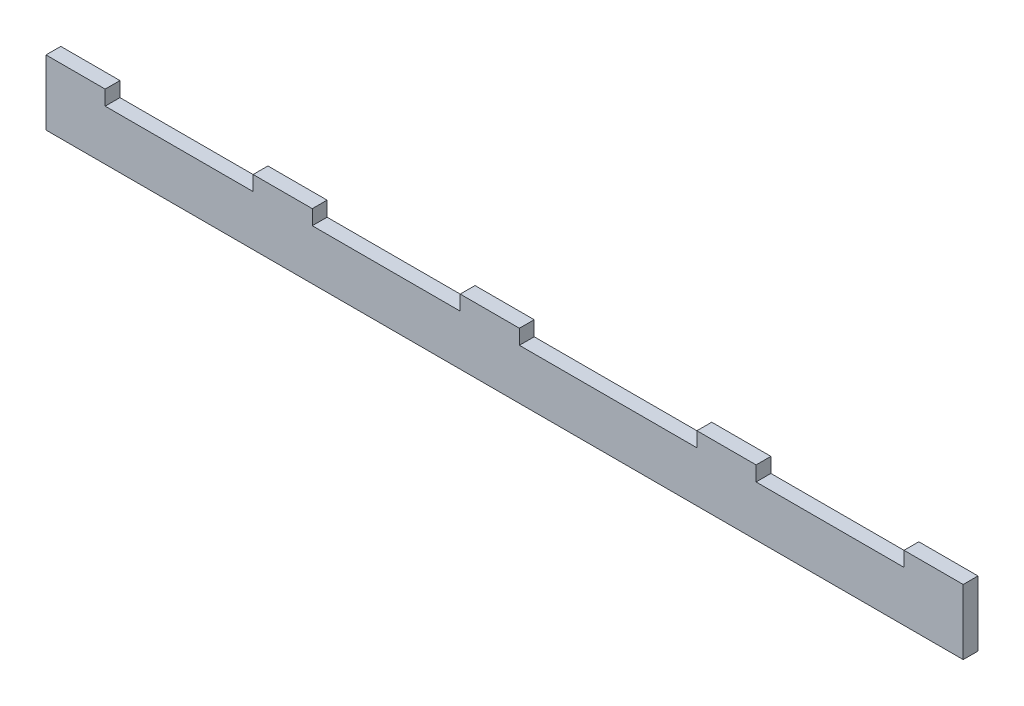
SolidWorks part; units mm, degrees
ref_plane "Plan de face" through (0, 0, 0) normal (0, 0, 1) x (1, 0, 0)
ref_plane "Plan de dessus" through (0, 0, 0) normal (0, 1, 0) x (1, 0, 0)
ref_plane "Plan de droite" through (0, 0, 0) normal (1, 0, 0) x (0, 0, -1)
sketch "Esquisse1" plane through (0, 0, 0) normal (0, 0, 1) x (1, 0, 0)
  line L0 (0, 0) -> (310, 0)
  line L1 (310, 0) -> (310, 22)
  line L2 (310, 22) -> (290, 22)
  line L3 (290, 22) -> (290, 17)
  line L4 (290, 17) -> (240, 17)
  line L5 (240, 17) -> (240, 22)
  line L6 (240, 22) -> (220, 22)
  line L7 (220, 22) -> (220, 17)
  line L8 (220, 17) -> (160, 17)
  line L9 (160, 17) -> (160, 22)
  line L10 (160, 22) -> (140, 22)
  line L11 (140, 22) -> (140, 17)
  line L12 (140, 17) -> (90, 17)
  line L13 (90, 17) -> (90, 22)
  line L14 (90, 22) -> (70, 22)
  line L15 (70, 22) -> (70, 17)
  line L16 (70, 17) -> (20, 17)
  line L17 (20, 17) -> (20, 22)
  line L18 (20, 22) -> (0, 22)
  line L19 (0, 22) -> (0, 0)
  dimension "D2" = 22
  dimension "D3" = 20
  dimension "D4" = 5
  dimension "D5" = 50
  dimension "D6" = 60
extrude "Boss.-Extru.2" add sketch "Esquisse1" along normal blind 5 contours L18 L19 L0 L1 L2 L3 L4 L5 L6 L7 L8 L9 L10 L11 L12 L13 L14 L15 L16 L17
